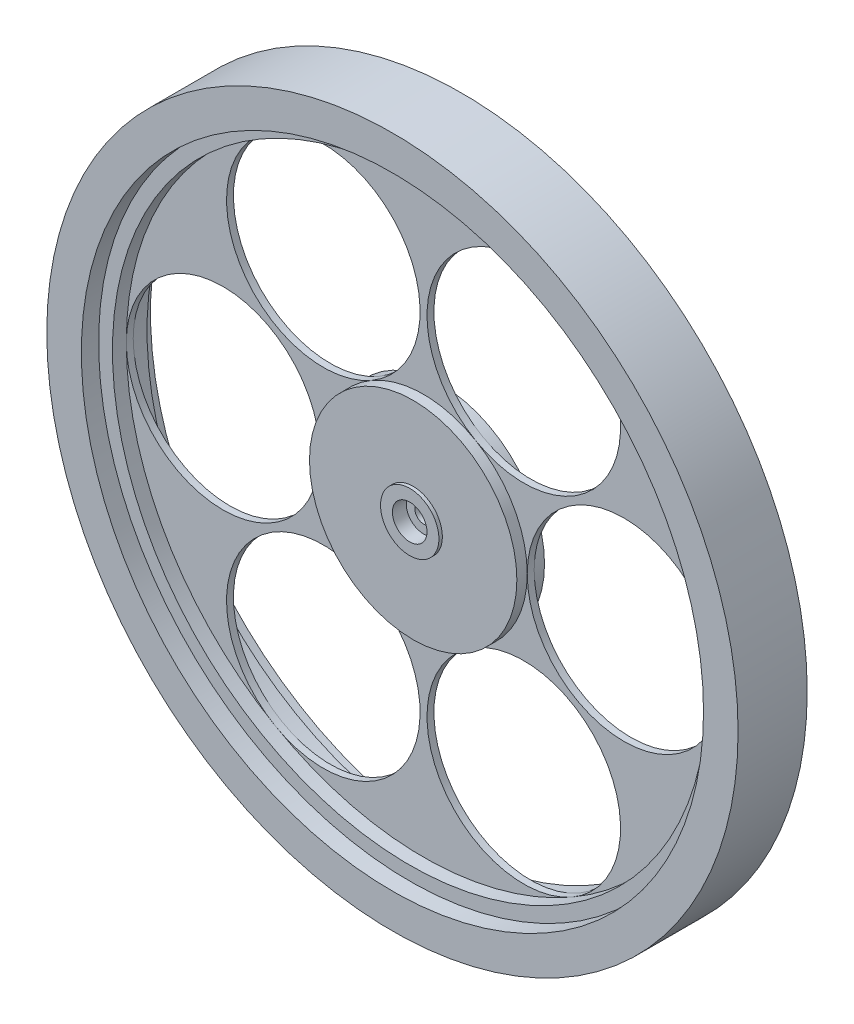
SolidWorks part; units mm, degrees
material "1060 Alloy"
ref_plane "Front Plane" through (0, 0, 0) normal (0, 0, 1) x (1, 0, 0)
ref_plane "Top Plane" through (0, 0, 0) normal (0, 1, 0) x (1, 0, 0)
ref_plane "Right Plane" through (0, 0, 0) normal (1, 0, 0) x (0, 0, -1)
sketch "Sketch1" plane through (0, 0, 0) normal (0, 0, 1) x (1, 0, 0)
  line L0 (0, 0) -> (63.5, 0) construction
  line L1 (0, 0) -> (31.75, 54.9926) construction
  line L2 (0, 0) -> (-27.305, 47.2936) construction
  line L3 (0, 0) -> (27.305, -47.2936) construction
  line L4 (0, 0) -> (-27.305, -47.2936) construction
  circle A0 centre (0, 0) radius 63.5
  circle A1 centre (0, 0) radius 57.15
  circle A2 centre (0, 0) radius 3.175
  circle A3 centre (0, 0) radius 5.364
  circle A4 centre (0, 0) radius 19.05
  circle A5 centre (0, 0) radius 54.61
  circle A6 centre (36.83, 0) radius 17.78
  circle A7 centre (18.415, 31.8957) radius 17.78
  circle A8 centre (-18.415, 31.8957) radius 17.78
  circle A9 centre (-36.83, 0) radius 17.78
  circle A10 centre (-18.415, -31.8957) radius 17.78
  circle A11 centre (18.415, -31.8957) radius 17.78
  circle A12 centre (0, 0) radius 1.5875
  dimension "D1" = 127
  dimension "D2" = 6.35
  dimension "D3" = 2.54
  dimension "D4" = 6.35
  dimension "D5" = 60
  dimension "D7" = 3.175
  dimension "D8" = 1.27
  dimension "D6" = 120
extrude "Boss-Extrude1" add sketch "Sketch1" along normal mid plane 1.27 contours A2 | A8 A4 A7 A5 | A9 A4 A8 A5 | A10 A4 A9 A5 | A11 A4 A10 A5 | A11 A5 A6 A4 | A7 A4 A6 A5 region at (-3.0852, 0, 0) region at (37.9018, -21.8826, 0) region at (37.9018, 21.8826, 0) region at (0, 43.7652, 0) region at (0, -43.7652, 0) region at (-37.9018, 21.8826, 0) region at (-37.9018, -21.8826, 0)
extrude "Boss-Extrude2" add sketch "Sketch1<3>" along normal mid plane 6.35 contours A3 A2 | A1 A5 region at (-55.5336, 0, 0) region at (-5.2122, 0, 0)
sketch "Sketch1<3>" plane through (0, 0, 0) normal (0, 0, 1) x (1, 0, 0) same geometry as "Sketch1"
extrude "Boss-Extrude4" add sketch "Sketch1<4>" along normal mid plane 5.08 contours A4 A3 region at (16.0312, -9.2556, 0)
sketch "Sketch1<4>" plane through (0, 0, 0) normal (0, 0, 1) x (1, 0, 0) same geometry as "Sketch1"
extrude "Boss-Extrude5" add sketch "Sketch1<5>" along normal mid plane 12.7 contours A0 A1 region at (-61.7039, 0, 0)
sketch "Sketch1<5>" plane through (0, 0, 0) normal (0, 0, 1) x (1, 0, 0) same geometry as "Sketch1"
